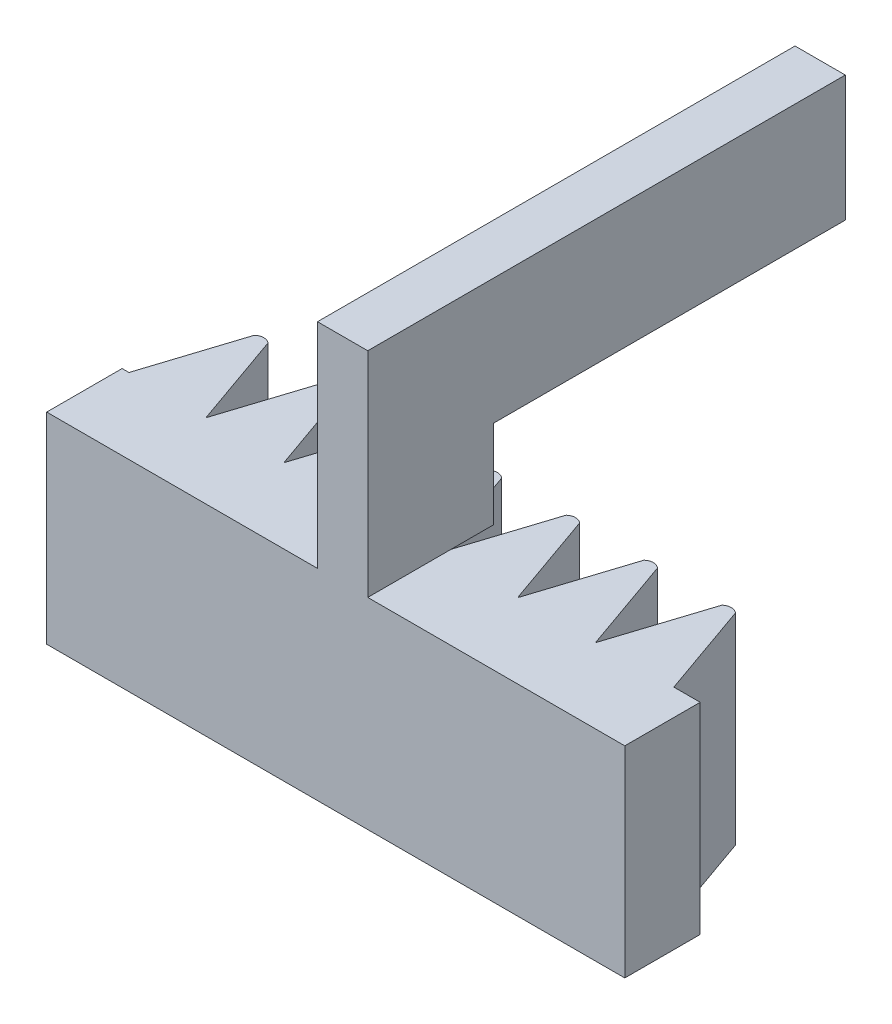
SolidWorks part; units mm, degrees
ref_plane "Front Plane" through (0, 0, 0) normal (0, 0, 1) x (1, 0, 0)
ref_plane "Top Plane" through (0, 0, 0) normal (0, 1, 0) x (1, 0, 0)
ref_plane "Right Plane" through (0, 0, 0) normal (1, 0, 0) x (0, 0, -1)
sketch "Base" plane through (0, 0, 0) normal (0, 1, 0) x (1, 0, 0)
  line L1 (-0.7735, 0) -> (22.2265, 0)
  line L2 (-0.7735, 0) -> (-0.7735, -3)
  line L3 (-0.7735, -3) -> (22.2265, -3)
  line L4 (22.2265, 0) -> (22.2265, -3)
  dimension "D1" = 23
  dimension "D2" = 3
sketch "Gears-1" plane through (0, 0, 0) normal (0, 1, 0) x (1, 0, 0)
  line L0 (-0.5006, 0) -> (0.7096, 3.7758)
  line L1 (-0.7735, 0) -> (22.2265, 0) construction
  line L2 (0.9805, 3.883) -> (0.9805, 2.653) construction
  line L3 (2.579, 0) -> (1.2514, 3.7758)
  line L4 (-0.5006, 0) -> (2.579, 0)
  line L5 (2.5994, 0) -> (5.679, 0)
  line L6 (5.679, 0) -> (4.3514, 3.7758)
  line L7 (2.5994, 0) -> (3.8096, 3.7758)
  line L8 (5.6994, 0) -> (8.779, 0)
  line L9 (8.779, 0) -> (7.4514, 3.7758)
  line L10 (5.6994, 0) -> (6.9096, 3.7758)
  line L11 (8.7994, 0) -> (11.879, 0)
  line L12 (11.879, 0) -> (10.5514, 3.7758)
  line L13 (8.7994, 0) -> (10.0096, 3.7758)
  line L14 (11.8994, 0) -> (14.979, 0)
  line L15 (14.979, 0) -> (13.6514, 3.7758)
  line L16 (11.8994, 0) -> (13.1096, 3.7758)
  line L17 (14.9994, 0) -> (18.079, 0)
  line L18 (18.079, 0) -> (16.7514, 3.7758)
  line L19 (14.9994, 0) -> (16.2096, 3.7758)
  line L20 (18.0994, 0) -> (21.179, 0)
  line L21 (21.179, 0) -> (19.8514, 3.7758)
  line L22 (18.0994, 0) -> (19.3096, 3.7758)
  arc A0 (0.7096, 3.7758) -> (1.2514, 3.7758) centre (0.9805, 3.4871) cw
  arc A1 (3.8096, 3.7758) -> (4.3514, 3.7758) centre (4.0805, 3.4871) cw
  arc A2 (6.9096, 3.7758) -> (7.4514, 3.7758) centre (7.1805, 3.4871) cw
  arc A3 (10.0096, 3.7758) -> (10.5514, 3.7758) centre (10.2805, 3.4871) cw
  arc A4 (13.1096, 3.7758) -> (13.6514, 3.7758) centre (13.3805, 3.4871) cw
  arc A5 (16.2096, 3.7758) -> (16.7514, 3.7758) centre (16.4805, 3.4871) cw
  arc A6 (19.3096, 3.7758) -> (19.8514, 3.7758) centre (19.5805, 3.4871) cw
  dimension "D1" = 7
extrude "Boss-Extrude1" add sketch "Gears-1" along normal blind 8
extrude "Boss-Extrude2" add sketch "Base" along normal blind 8
ref_plane "Plane1" through (10, 0, 0) normal (1, 0, 0) x (0, 0, -1)
sketch "Sketch1" plane through (10, 0, 0) normal (1, 0, 0) x (0, 0, -1)
  line L1 (-3, 8) -> (2, 8)
  line L2 (-3, 8) -> (-3, 16.5)
  line L3 (-3, 16.5) -> (2, 16.5)
  line L4 (2, 8) -> (2, 16.5)
  dimension "D1" = 8.5
  dimension "D2" = 5
extrude "Boss-Extrude3" add sketch "Sketch1" along normal blind 2
sketch "Sketch2" plane through (0, 0, -2) normal (0, 0, -1) x (-1, 0, 0)
  line L0 (-10, 8) -> (-10, 16.5) construction
  line L1 (-12, 16.5) -> (-10, 16.5)
  line L2 (-12, 16.5) -> (-12, 11.5)
  line L3 (-12, 11.5) -> (-10, 11.5)
  line L4 (-10, 16.5) -> (-10, 11.5)
  dimension "D1" = 5
extrude "Boss-Extrude4" add sketch "Sketch2" along normal blind 14
